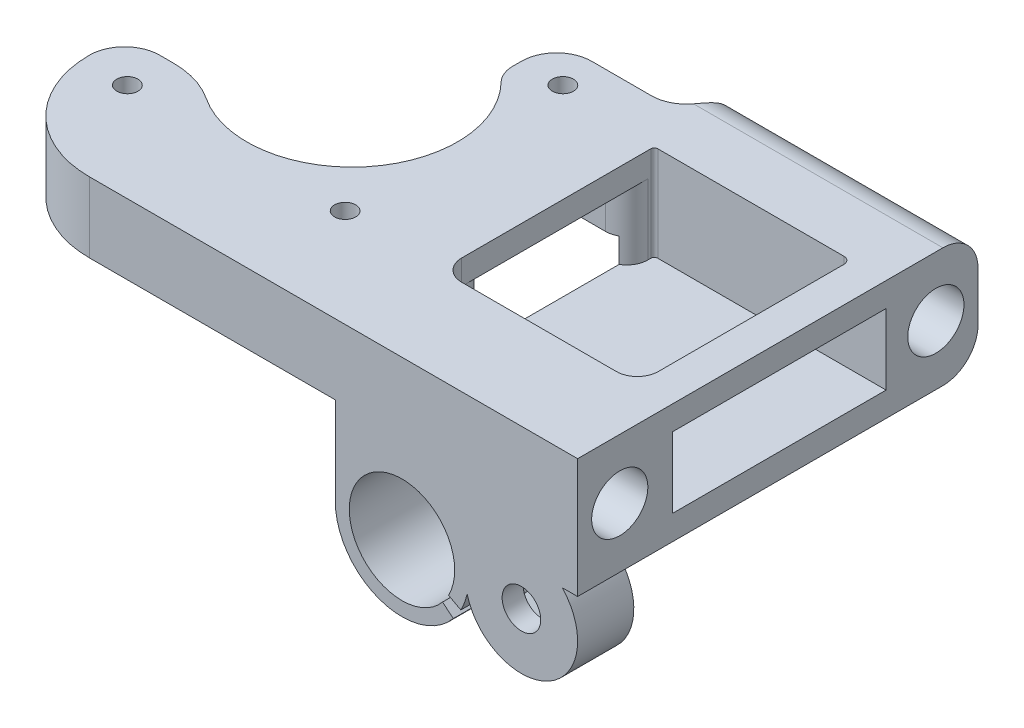
SolidWorks part; units mm, degrees
material "ABS generico"
ref_plane "Front Plane" through (0, 0, 0) normal (0, 0, 1) x (1, 0, 0)
ref_plane "Top Plane" through (0, 0, 0) normal (0, 1, 0) x (1, 0, 0)
ref_plane "Right Plane" through (0, 0, 0) normal (1, 0, 0) x (0, 0, -1)
sketch "Sketch1" plane through (0, 0, 0) normal (0, 0, 1) x (1, 0, 0)
  line L0 (73.5, -17) -> (73.5, 0)
  line L1 (43.3893, -17) -> (39, -17)
  line L2 (39, -17) -> (39, -22.5) construction
  line L3 (65.5, -18.2276) -> (61.8, -20.3638) construction
  line L4 (61.8, -20.3638) -> (61.8, -24.6362) construction
  line L7 (73.5, -17) -> (53.6024, -17)
  line L8 (61.8, -24.6362) -> (65.5, -26.7724) construction
  line L10 (39, 0) -> (73.5, 0)
  line L11 (57.9584, -23.294) -> (57.9584, -17) construction
  line L12 (65.5, -26.7724) -> (69.2, -24.6362) construction
  line L13 (69.2, -24.6362) -> (69.2, -20.3638) construction
  line L14 (54.2695, -27.2923) -> (55.8016, -28.5649) construction
  line L15 (39, -17) -> (39, 0)
  line L16 (56.8764, -26.9641) -> (55.1187, -26.0274) construction
  line L17 (69.2, -20.3638) -> (65.5, -18.2276) construction
  circle A0 centre (65.5, -22.5) radius 3.7 construction
  arc A1 (57.7674, -24.5509) -> (71.3095, -17) centre (65.5, -22.5) ccw construction
  arc A2 (43.3893, -17) -> (53.6024, -17) centre (48.4959, -22.4988) ccw construction
  circle A3 centre (65.5, -22.5) radius 2.75 construction
  arc A4 (55.8016, -28.5649) -> (39, -22.5) centre (48.4959, -22.4988) cw construction
  arc A6 (57.9584, -23.294) -> (56.8764, -26.9641) centre (48.4959, -22.4988) cw construction
  arc A7 (43.3893, -17) -> (53.6024, -17) centre (48.4959, -22.4988) cw
  dimension "D2" = 5.5
  dimension "D3" = 34.5
  dimension "D1" = 7.4
  dimension "D4" = 17
extrude "Extrude1" add sketch "Sketch1" against normal blind 57
sketch "Sketch2" plane through (0, 0, 0) normal (0, 0, 1) x (1, 0, 0)
  line L0 (57.9584, -23.294) -> (57.9584, -17) construction
  line L1 (73.5, -17) -> (53.6024, -17) construction
  line L2 (57.9584, -23.294) -> (57.9584, -17)
  line L3 (71.3095, -17) -> (57.9584, -17)
  arc A1 (56.8764, -26.9641) -> (57.9584, -23.294) centre (48.4959, -22.4988) ccw construction
  arc A2 (57.7674, -24.5509) -> (71.3095, -17) centre (65.5, -22.5) ccw construction
  circle A3 centre (65.5, -22.5) radius 2.75 construction
  arc A4 (57.7674, -24.5509) -> (57.9584, -23.294) centre (48.4959, -22.4988) ccw
  arc A5 (57.7674, -24.5509) -> (71.3095, -17) centre (65.5, -22.5) ccw
  circle A6 centre (65.5, -22.5) radius 2.75
extrude "Extrude2" add sketch "Sketch2" against normal blind 8
sketch "Sketch3" plane through (0, 0, -8) normal (0, 0, -1) x (-1, 0, 0)
  line L6 (-69.5, -20.1906) -> (-65.5, -17.8812)
  line L7 (-65.5, -17.8812) -> (-61.5, -20.1906)
  line L8 (-61.5, -20.1906) -> (-61.5, -24.8094)
  line L9 (-61.5, -24.8094) -> (-65.5, -27.1188)
  line L10 (-65.5, -27.1188) -> (-69.5, -24.8094)
  line L11 (-69.5, -24.8094) -> (-69.5, -20.1906)
extrude "Extrude3" cut sketch "Sketch3" against normal blind 5
sketch "Sketch4" plane through (0, 0, 0) normal (0, 0, 1) x (1, 0, 0)
  line L0 (39, -17) -> (39, -22.5) construction
  line L1 (43.3893, -17) -> (39, -17) construction
  line L2 (56.8764, -26.9641) -> (55.1187, -26.0274) construction
  line L3 (54.2695, -27.2923) -> (55.8016, -28.5649) construction
  line L4 (57.9584, -23.294) -> (57.9584, -17) construction
  line L5 (73.5, -17) -> (53.6024, -17) construction
  line L6 (39, -17) -> (39, -22.5)
  line L7 (43.3893, -17) -> (39, -17)
  line L8 (56.8764, -26.9641) -> (55.1187, -26.0274)
  line L9 (54.2695, -27.2923) -> (55.8016, -28.5649)
  line L10 (57.9584, -23.294) -> (57.9584, -17)
  line L11 (57.9584, -17) -> (53.6024, -17)
  arc A0 (43.3893, -17) -> (53.6024, -17) centre (48.4959, -22.4988) ccw construction
  arc A1 (56.8764, -26.9641) -> (57.9584, -23.294) centre (48.4959, -22.4988) ccw construction
  arc A2 (39, -22.5) -> (55.8016, -28.5649) centre (48.4959, -22.4988) ccw construction
  arc A3 (43.3893, -17) -> (54.2695, -27.2923) centre (48.4959, -22.4988) ccw
  arc A4 (56.8764, -26.9641) -> (57.9584, -23.294) centre (48.4959, -22.4988) ccw
  arc A5 (39, -22.5) -> (55.8016, -28.5649) centre (48.4959, -22.4988) ccw
  arc A6 (55.1187, -26.0274) -> (53.6024, -17) centre (48.4959, -22.4988) ccw
extrude "Extrude4" add sketch "Sketch4" against normal blind 50
sketch "Sketch5" plane through (73.5, 0, 0) normal (1, 0, 0) x (0, 0, -1)
  line L0 (0, -8.5) -> (57, -8.5) construction
  line L1 (0, -17) -> (0, 0) construction
  line L2 (57, -17) -> (57, 0) construction
  line L3 (28.5, 0) -> (28.5, -17) construction
  line L4 (57, 0) -> (0, 0) construction
  line L5 (57, -17) -> (0, -17) construction
  line L7 (13.5, -13.5) -> (43.5, -13.5)
  line L8 (13.5, -13.5) -> (13.5, -3.5)
  line L9 (13.5, -3.5) -> (43.5, -3.5)
  line L10 (43.5, -13.5) -> (43.5, -3.5)
  line L11 (13.5, -13.5) -> (43.5, -3.5) construction
  line L12 (13.5, -3.5) -> (43.5, -13.5) construction
  circle A0 centre (6, -8.5) radius 4
  circle A1 centre (51, -8.5) radius 4
  point P12 (28.5, -8.5)
  dimension "D4" = 8
  dimension "D1" = 10
  dimension "D2" = 30
  dimension "D3" = 22.5
extrude "Extrude5" cut sketch "Sketch5" against normal blind 33 contours A0 | A1
sketch "Sketch6" plane through (73.5, 0, 0) normal (1, 0, 0) x (0, 0, -1)
  line L0 (13.5, -13.5) -> (13.5, -3.5) construction
  line L1 (13.5, -3.5) -> (43.5, -3.5) construction
  line L2 (43.5, -13.5) -> (43.5, -3.5) construction
  line L3 (13.5, -13.5) -> (43.5, -13.5) construction
  line L4 (13.5, -13.5) -> (13.5, -3.5)
  line L5 (13.5, -3.5) -> (43.5, -3.5)
  line L6 (43.5, -13.5) -> (43.5, -3.5)
  line L7 (13.5, -13.5) -> (43.5, -13.5)
extrude "Extrude6" cut sketch "Sketch6" against normal blind 33
sketch "Sketch7" plane through (39, 0, 0) normal (-1, 0, 0) x (0, 0, 1)
  line L0 (0, -17) -> (0, 0) construction
  line L4 (0, 0) -> (0, -10)
  line L6 (-50, 0) -> (-50, -10)
  line L8 (-50, -10) -> (0, -10)
  line L11 (-50, 0) -> (0, 0)
extrude "Extrude7" add sketch "Sketch7" along normal blind 50
sketch "Sketch10" plane through (0, -10, 0) normal (0, -1, 0) x (1, 0, 0)
  line L0 (26.4008, 4.2075) -> (26.4008, -61.311) construction
  line L2 (-4.5992, 4.2075) -> (-4.5992, -61.311) construction
  line L3 (-23.5897, 0) -> (85.8099, 0) construction
  line L4 (-23.5897, -14) -> (85.8099, -14) construction
  line L5 (-23.5897, -45) -> (85.8099, -45) construction
  circle A0 centre (-4.5992, -45) radius 1.5
  circle A1 centre (26.4008, -45) radius 1.5
  circle A2 centre (26.4008, -14) radius 1.5
  circle A3 centre (-4.5992, -14) radius 1.5
  dimension "D4" = 3
  dimension "D1" = 31
  dimension "D2" = 14
  dimension "D3" = 31
  dimension "D5" = 2
  dimension "D6" = 2
extrude "Extrude10" cut sketch "Sketch10" against normal up to surface (10 mm away) up to face at (29.6667, 0, -36.25)
sketch "Sketch11" plane through (0, -10, 0) normal (0, -1, 0) x (1, 0, 0)
  circle A0 centre (-4.5992, -14) radius 2.75
  circle A1 centre (26.4008, -14) radius 2.75
  circle A2 centre (26.4008, -45) radius 2.75
  circle A4 centre (-4.5992, -45) radius 2.75 [skipped]
  dimension "D1" = 5.5
  dimension "D2" = 2
  dimension "D3" = 2
extrude "Extrude13" cut sketch "Sketch11" against normal blind 1
sketch "Sketch12" plane through (0, -10, 0) normal (0, -1, 0) x (1, 0, 0)
  line L1 (-4.5992, -14) -> (26.4008, -14) construction
  line L2 (-4.5992, -14) -> (-4.5992, -45) construction
  line L3 (-4.5992, -45) -> (26.4008, -45) construction
  line L4 (26.4008, -14) -> (26.4008, -45) construction
  circle A0 centre (10.9008, -30.5) radius 15
  dimension "D1" = 30
extrude "Extrude14" cut sketch "Sketch12" against normal up to surface (10 mm away) up to face at (-4.5992, 0, -12.5)
fillet "Fillet2" radius 5 3 edges at (41.1947, -17, -57) (63.5512, -17, -57) (48.4959, -14.9946, -57)
fillet "Fillet3" radius 5 1 edges at (56.25, 0, -57)
fillet "Fillet4" radius 10 1 edges at (57, -13.5, -43.5)
sketch "Sketch13" plane through (0, -17, 0) normal (0, -1, 0) x (1, 0, 0)
  line L1 (57.9584, -16.1375) -> (57.9584, -43.8625)
  line L2 (57.9584, -50) -> (57.9584, -8) construction
  arc A0 (57.9584, -43.8625) -> (57.9584, -16.1375) centre (55.9998, -30) ccw
extrude "Extrude15" cut sketch "Sketch13" against normal up to surface (17 mm away) up to face at (10.9008, 0, -15.5)
sketch "Sketch14" plane through (40.5, 0, 0) normal (1, 0, 0) x (0, 0, -1)
  line L4 (40, -3.5) -> (20, -3.5)
  line L5 (40, -3.5) -> (40, -13.5)
  line L6 (40, -13.5) -> (20, -13.5)
  line L7 (20, -3.5) -> (20, -13.5)
  point P1 (30, -8.5)
  dimension "D1" = 20
extrude "Extrude16" cut sketch "Sketch14" against normal blind 60
sketch "Sketch15" plane through (0, 0, 0) normal (0, 1, 0) x (1, 0, 0)
  line L0 (2.1139, 20) -> (-12.4389, 20)
  line L1 (-12.4389, 50) -> (20.4964, 50)
  line L2 (2.1139, 40) -> (2.1139, 20)
  line L3 (-12.4389, 20) -> (-12.4389, 50)
  line L5 (20.4964, 40) -> (20.4964, 50)
  line L6 (2.1139, 40) -> (20.4964, 40)
extrude "Extrude18" cut sketch "Sketch15" against normal blind 60
fillet "Fillet5" radius 10 1 edges at (57, -13.5, -13.5)
fillet "Fillet7" radius 3 2 edges
fillet "Fillet8" radius 5 1 edges at (-11, -5, -20)
fillet "Fillet9" radius 5 1 edges at (20.4964, -5, -50)
sketch "Sketch16" plane through (0, -10, 0) normal (0, -1, 0) x (1, 0, 0)
  circle A0 centre (10.9008, -23) radius 11.3049
extrude "Extrude19" cut sketch "Sketch16" against normal blind 6.5
fillet "Fillet11" radius 12 3 edges at (0.1887, -1.75, -20) (0.0013, -6.75, -20) (0.095, -3.5, -20)
fillet "Fillet12" radius 10 2 edges at (0.2489, -6.75, -19.2135) (21.8003, -6.75, -20)
fillet "Fillet13" radius 4 1 edges at (20.4964, -5, -42.0293)
fillet "Fillet14" radius 5 1 edges at (22.509, -6.75, -40)
fillet "Fillet15" radius 5 1 edges
sketch "Sketch17" plane through (0, -10, 0) normal (0, -1, 0) x (1, 0, 0)
  line L2 (-11, 0) -> (39, 0) construction
  line L3 (-11, -15) -> (-11, 0) construction
  line L4 (4, 0) -> (4, 2.3729)
  line L5 (4, 2.3729) -> (-13.4091, 2.3729)
  line L6 (-13.4091, 2.3729) -> (-13.4091, -15)
  line L7 (-13.4091, -15) -> (-11, -15)
  arc A1 (4, 0) -> (-11, -15) centre (4, -15) ccw
  dimension "D1" = 30
extrude "Extrude21" cut sketch "Sketch17" against normal blind 10
sketch "Schizzo1" plane through (73.5, 0, 0) normal (1, 0, 0) x (0, 0, -1)
  line L1 (52, 0) -> (0, 0) construction
  line L3 (13.5, 0) -> (43.9157, 0)
  line L4 (13.5, 0) -> (13.5, -13.5)
  line L5 (13.5, -13.5) -> (43.9157, -13.5)
  line L6 (43.9157, 0) -> (43.9157, -13.5)
extrude "Taglio-Estrusione1" cut sketch "Schizzo1" against normal up to surface (33 mm away) up to face at (40.5, -6.161, -16.139)
fillet "Raccordo1" radius 3 1 edges at (40.5, -6.75, -13.5)
fillet "Raccordo2" radius 0.5 1 edges at (40.5, -6.75, -43.9157)
sketch "Schizzo2" plane through (73.5, 0, 0) normal (1, 0, 0) x (0, 0, -1)
  line L0 (43.9157, 0) -> (43.9157, -13.5) construction
  line L1 (13.5, 0) -> (43.9157, 0)
  line L2 (13.5, 0) -> (13.5, -3.4438)
  line L3 (13.5, -3.4438) -> (43.9157, -3.4438)
  line L4 (43.9157, 0) -> (43.9157, -3.4438)
extrude "Estrusione-Estrusione1" add sketch "Schizzo2" against normal blind 5
fillet "Raccordo3" radius 1 1 edges at (68.5, -1.7219, -43.9157)
fillet "Raccordo4" radius 3 1 edges at (68.5, -1.7219, -13.5)
sketch "Schizzo3" plane through (0, -17, 0) normal (0, -1, 0) x (1, 0, 0)
  line L0 (57.9584, -16.1375) -> (57.9584, -8) construction
  line L1 (57.9584, -13.9275) -> (70.6682, -13.9275)
  line L2 (57.9584, -13.9275) -> (57.9584, -44.3979)
  line L3 (57.9584, -44.3979) -> (70.6682, -44.3979)
  line L4 (70.6682, -13.9275) -> (70.6682, -44.3979)
extrude "Estrusione-Estrusione2" add sketch "Schizzo3" against normal up to surface (3.5 mm away) up to face at (47.1123, -13.5, -30.793)
